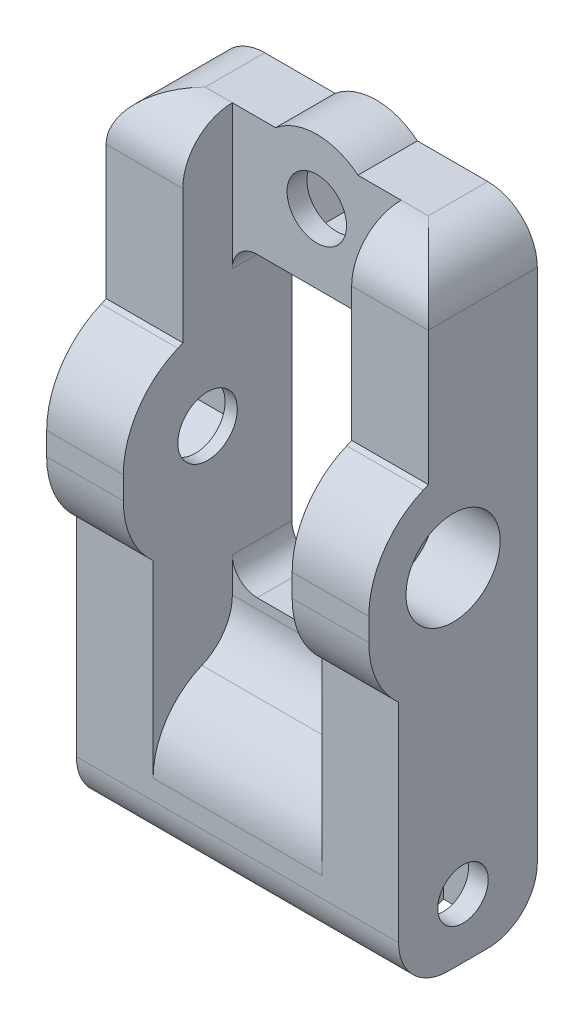
SolidWorks part; units mm, degrees
ref_plane "Front Plane" through (0, 0, 0) normal (0, 0, 1) x (1, 0, 0)
ref_plane "Top Plane" through (0, 0, 0) normal (0, 1, 0) x (1, 0, 0)
ref_plane "Right Plane" through (0, 0, 0) normal (1, 0, 0) x (0, 0, -1)
ref_plane "Plane1" through (31.766, 0, 0) normal (1, 0, 0) x (0, 0, -1)
sketch "Sketch1" plane through (31.766, 0, 0) normal (1, 0, 0) x (0, 0, -1)
  line L0 (-14, 26) -> (-14, 32.7082)
  line L1 (-14, 32.7082) -> (-17, 32.7082)
  arc A0 (-17, 32.7082) -> (-14, 26) centre (-8, 32.7082) ccw
extrude "Boss-Extrude1" add sketch "Sketch1" against normal blind 32.5
sketch "Sketch2" plane through (0, 0, 14) normal (0, 0, -1) x (-1, 0, 0)
  line L0 (-31.766, 32.7082) -> (0.734, 32.7082)
  line L1 (0.734, 32.7082) -> (0.734, 7)
  line L2 (0.734, 7) -> (-31.766, 7)
  line L3 (-31.766, 7) -> (-31.766, 32.7082)
extrude "Boss-Extrude2" add sketch "Sketch2" along normal blind 8
ref_plane "Plane2" through (24.032, 0, 0) normal (1, 0, 0) x (0, 0, -1)
sketch "Sketch3" plane through (24.032, 0, 0) normal (1, 0, 0) x (0, 0, -1)
  line L0 (-6, 15) -> (-6, 32.7082)
  line L1 (-6, 32.7082) -> (-17, 32.7082)
  line L2 (-14, 26) -> (-14, 7)
  arc A0 (-17, 32.7082) -> (-14, 26) centre (-8, 32.7082) ccw
  arc A1 (-14, 7) -> (-6, 15) centre (-6, 7) cw
extrude "Cut-Extrude1" cut sketch "Sketch3" against normal blind 17.032
sketch "Sketch4" plane through (0, 7, 0) normal (0, -1, 0) x (1, 0, 0)
  line L0 (31.766, 6) -> (-0.734, 6)
  line L1 (-0.734, 6) -> (-0.734, 14)
  line L2 (-0.734, 14) -> (31.766, 14)
  line L3 (31.766, 14) -> (31.766, 6)
extrude "Boss-Extrude3" add sketch "Sketch4" along normal blind 7
sketch "Sketch5" plane through (0, 32.7082, 0) normal (0, 1, 0) x (-1, 0, 0)
  line L0 (-24.032, 6) -> (-31.766, 6)
  line L1 (-31.766, 6) -> (-31.766, 17)
  line L2 (-31.766, 17) -> (-24.032, 17)
  line L3 (-24.032, 17) -> (-24.032, 6)
extrude "Boss-Extrude4" add sketch "Sketch5" along normal blind 29.2918
sketch "Sketch6" plane through (0, 32.7082, 0) normal (0, 1, 0) x (-1, 0, 0)
  line L0 (0.734, 6) -> (-7, 6)
  line L1 (-7, 6) -> (-7, 17)
  line L2 (-7, 17) -> (0.734, 17)
  line L3 (0.734, 17) -> (0.734, 6)
extrude "Boss-Extrude5" add sketch "Sketch6" along normal blind 29.2918
sketch "Sketch7" plane through (0, 0, 6) normal (0, 0, -1) x (-1, 0, 0)
  line L0 (-7, 50) -> (-24.032, 50)
  line L1 (-24.032, 50) -> (-24.032, 20)
  line L2 (-24.032, 20) -> (-7, 20)
  line L3 (-7, 20) -> (-7, 50)
  line L4 (0.734, 62) -> (0.734, 0)
  line L5 (0.734, 0) -> (-31.766, 0)
  line L6 (-31.766, 0) -> (-31.766, 62)
  line L7 (-31.766, 62) -> (-19.6693, 62)
  line L8 (-11.3627, 62) -> (0.734, 62)
  arc A0 (-19.6693, 62) -> (-11.3627, 62) centre (-15.516, 57) cw
extrude "Boss-Extrude6" add sketch "Sketch7" along normal blind 6
sketch "Sketch9" plane through (31.766, 0, 0) normal (1, 0, 0) x (0, 0, -1)
  line L0 (-11, 43.5209) -> (-11, 62)
  line L1 (-11, 62) -> (-17, 62)
  line L2 (-17, 62) -> (-17, 35)
  arc A0 (-17, 35) -> (-11.5, 43.2916) centre (-8, 35) cw
  arc A1 (-11.5, 43.2916) -> (-11, 43.5209) centre (-15, 51.5831) ccw
extrude "Cut-Extrude3" cut sketch "Sketch9" against normal up to surface (32.5 mm away) up to face at (-0.734, 28.8437, 10.5833)
sketch "Sketch10" plane through (-0.734, 0, 0) normal (-1, 0, 0) x (0, 0, 1)
  line L0 (8.5, 40.0518) -> (4.125, 37.5259)
  line L1 (4.125, 37.5259) -> (4.125, 32.4741)
  line L2 (4.125, 32.4741) -> (8.5, 29.9482)
  line L3 (8.5, 29.9482) -> (12.875, 32.4741)
  line L4 (12.875, 32.4741) -> (12.875, 37.5259)
  line L5 (12.875, 37.5259) -> (8.5, 40.0518)
extrude "Cut-Extrude4" cut sketch "Sketch10" against normal blind 6.5
sketch "Sketch11" plane through (0, 0, 0) normal (0, 0, -1) x (-1, 0, 0)
  line L0 (-17.8356, 61.1) -> (-20.2028, 57)
  line L1 (-20.2028, 57) -> (-17.8356, 52.9)
  line L2 (-17.8356, 52.9) -> (-13.1014, 52.9)
  line L3 (-13.1014, 52.9) -> (-10.7342, 57)
  line L4 (-10.7342, 57) -> (-13.1014, 61.1)
  line L5 (-13.1014, 61.1) -> (-17.8356, 61.1)
extrude "Cut-Extrude5" cut sketch "Sketch11" against normal blind 4
sketch "Sketch12" plane through (0, 0, 0) normal (0, -1, 0) x (1, 0, 0)
  line L0 (29.766, 3.25) -> (29.766, 11.75)
  line L1 (29.766, 11.75) -> (25.566, 11.75)
  line L2 (25.566, 11.75) -> (25.566, 3.25)
  line L3 (25.566, 3.25) -> (29.766, 3.25)
extrude "Cut-Extrude6" cut sketch "Sketch12" against normal blind 12.5
sketch "Sketch13" plane through (0, 0, 0) normal (0, -1, 0) x (1, 0, 0)
  line L0 (5.466, 3.25) -> (5.466, 11.75)
  line L1 (5.466, 11.75) -> (1.266, 11.75)
  line L2 (1.266, 11.75) -> (1.266, 3.25)
  line L3 (1.266, 3.25) -> (5.466, 3.25)
extrude "Cut-Extrude7" cut sketch "Sketch13" against normal blind 12.5
hole_wizard "Ø5.1 (5.1) Diameter Hole1" positions "Sketch15" profile "Sketch14" hole size "Ø5.1" standard "ANSI Metric"
sketch "Sketch15" plane through (31.766, 0, 0) normal (1, 0, 0) x (0, 0, -1)
  point P0 (-7.5, 6)
sketch "Sketch14" plane through (31.766, 6, 7.5) normal (0, 1, 0) x (0, 0, -1)
  line L0 (0, 0) -> (0, 2)
  line L1 (0, 2) -> (2.55, 2)
  line L2 (2.55, 2) -> (2.55, 0)
  line L5 (2.55, 0) -> (0, 0)
  line L11 (0, -6.35) -> (0, 107.95) construction
  dimension "Thru Hole Dia." = 5.1
  dimension "Thru Hole Depth" = 2
hole_wizard "Ø5.1 (5.1) Diameter Hole2" positions "Sketch17" profile "Sketch16" hole size "Ø5.1" standard "ANSI Metric"
sketch "Sketch17" plane through (-0.734, 0, 0) normal (-1, 0, 0) x (0, 0, 1)
  point P0 (7.5, 6)
sketch "Sketch16" plane through (-0.734, 6, 7.5) normal (0, 1, 0) x (0, 0, 1)
  line L0 (0, 0) -> (0, 2)
  line L1 (0, 2) -> (2.55, 2)
  line L2 (2.55, 2) -> (2.55, 0)
  line L5 (2.55, 0) -> (0, 0)
  line L11 (0, -6.35) -> (0, 107.95) construction
  dimension "Thru Hole Dia." = 5.1
  dimension "Thru Hole Depth" = 2
hole_wizard "Ø6.0 (6) Diameter Hole1" positions "Sketch19" profile "Sketch18" hole size "Ø6.0" standard "ANSI Metric"
sketch "Sketch19" plane through (7, 0, 0) normal (1, 0, 0) x (0, 0, -1)
  point P0 (-8.5, 35)
sketch "Sketch18" plane through (7, 35, 8.5) normal (0, 1, 0) x (0, 0, -1)
  line L0 (0, 0) -> (0, 7.7341)
  line L1 (0, 7.7341) -> (3, 7.7341)
  line L2 (3, 7.7341) -> (3, 0)
  line L5 (3, 0) -> (0, 0)
  line L11 (0, -6.35) -> (0, 107.95) construction
  dimension "Thru Hole Dia." = 6
  dimension "Thru Hole Depth" = 7.734
hole_wizard "Hole1" positions "Sketch21" profile "Sketch20" legacy
sketch "Sketch21" plane through (31.766, 0, 0) normal (1, 0, 0) x (0, 0, -1)
  point P0 (-8.5, 35)
sketch "Sketch20" plane through (31.766, 35, 8.5) normal (0, 1, 0) x (0, 0, -1)
  line L0 (0, 0) -> (0, 32.5001)
  line L1 (0, 32.5001) -> (3, 32.5001)
  line L2 (3, 32.5001) -> (3, 6.5)
  line L3 (3, 6.5) -> (4.75, 6.5)
  line L4 (4.75, 6.5) -> (4.75, 0)
  line L5 (4.75, 0) -> (0, 0)
  line L6 (0, 110) -> (0, -10) construction
  dimension "Diameter" = 6
  dimension "Depth" = 32.5001
  dimension "C-Bore Diameter" = 9.5
  dimension "C-Bore Depth" = 6.5
hole_wizard "Ø6.0 (6) Diameter Hole2" positions "Sketch23" profile "Sketch22" hole size "Ø6.0" standard "ANSI Metric"
sketch "Sketch23" plane through (0, 0, 6) normal (0, 0, 1) x (1, 0, 0)
  point P0 (15.516, 57)
sketch "Sketch22" plane through (15.516, 57, 6) normal (1, 0, 0) x (0, -1, 0)
  line L0 (0, 0) -> (0, 1.999)
  line L1 (0, 1.999) -> (3, 1.999)
  line L2 (3, 1.999) -> (3, 0)
  line L5 (3, 0) -> (0, 0)
  line L10 (0, 1.999) -> (-3, 1.999) construction
  line L11 (0, -6.35) -> (0, 107.95) construction
  dimension "Hole Dia." = 6
  dimension "Hole Depth" = 1.999
  dimension "Drill Angle" = 180
hole_wizard "Ø5.1 (5.1) Diameter Hole3" positions "Sketch25" profile "Sketch24" hole size "Ø5.1" standard "ANSI Metric"
sketch "Sketch25" plane through (5.466, 0, 0) normal (-1, 0, 0) x (0, 0, 1)
  point P0 (7.5, 6)
sketch "Sketch24" plane through (5.466, 6, 7.5) normal (0, 1, 0) x (0, 0, 1)
  line L0 (0, 0) -> (0, 26.3001)
  line L1 (0, 26.3001) -> (2.55, 26.3001)
  line L2 (2.55, 26.3001) -> (2.55, 0)
  line L5 (2.55, 0) -> (0, 0)
  line L11 (0, -6.35) -> (0, 107.95) construction
  dimension "Thru Hole Dia." = 5.1
  dimension "Thru Hole Depth" = 26.3001
fillet "Fillet1" radius 2.5 4 edges tangent propagation no
fillet "Fillet2" radius 5 7 edges at (-0.734, 62, 5.5) (15.516, 0, 0) (27.899, 62, 11) (31.766, 62, 5.5) (15.516, 15, 6) (15.516, 0, 14) (3.133, 62, 11) tangent propagation no
ref_plane "Plane3" through (15.516, 0, 0) normal (1, 0, 0) x (0, 0, -1)
